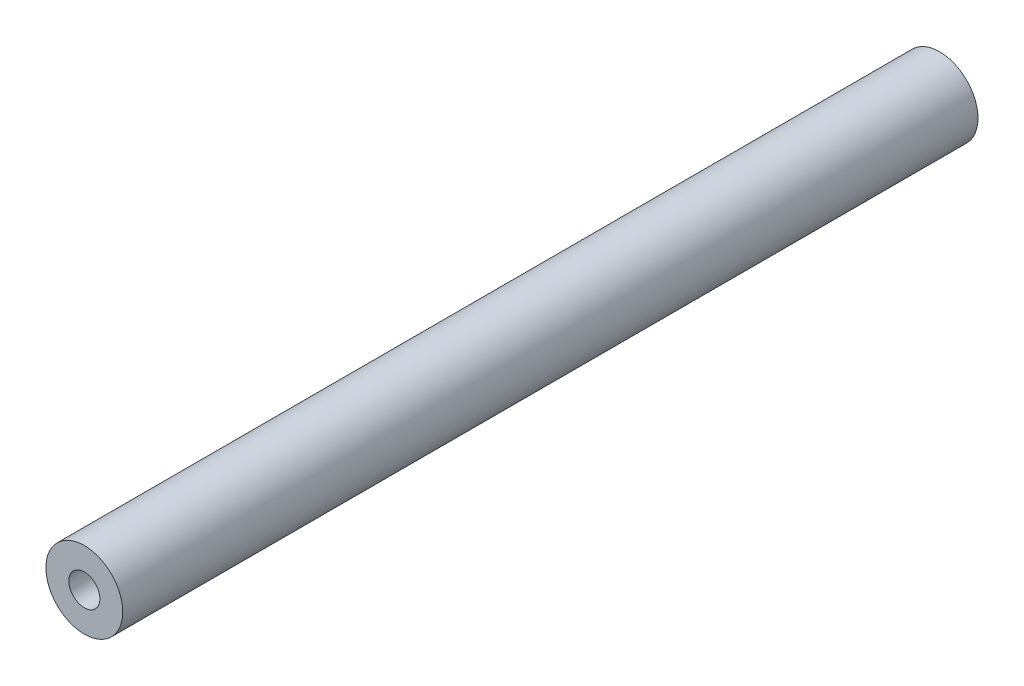
SolidWorks part; units mm, degrees
material "6061-T6 (SS)"
ref_plane "Front Plane" through (0, 0, 0) normal (0, 0, 1) x (1, 0, 0)
ref_plane "Top Plane" through (0, 0, 0) normal (0, 1, 0) x (1, 0, 0)
ref_plane "Right Plane" through (0, 0, 0) normal (1, 0, 0) x (0, 0, -1)
sketch "Sketch1" plane through (0, 0, 0) normal (0, 0, 1) x (1, 0, 0)
  circle A0 centre (0, 0) radius 6.4
  dimension "D1" = 12.8
extrude "Boss-Extrude1" add sketch "Sketch1" along normal blind 142.53
hole_wizard "#6 (0.204) Diameter Hole1" positions "Sketch2" profile "Sketch3" hole size "#6" standard "ANSI Inch"
sketch "Sketch2" plane through (0, 0, 0) normal (0, 0, -1) x (-1, 0, 0)
  point P0 (0, 0)
sketch "Sketch3" plane through (0, 0, 0) normal (1, 0, 0) x (0, 1, 0)
  line L0 (0, 0) -> (0, 31.5567)
  line L1 (0, 31.5567) -> (2.5908, 30)
  line L2 (2.5908, 30) -> (2.5908, 0)
  line L5 (2.5908, 0) -> (0, 0)
  line L10 (0, 31.5567) -> (-2.5908, 30) construction
  line L11 (0, -6.35) -> (0, 107.95) construction
  dimension "Hole Dia." = 5.1816
  dimension "Hole Depth" = 30
  dimension "Drill Angle" = 118
hole_wizard "#6 (0.204) Diameter Hole2" positions "Sketch4" profile "Sketch5" hole size "#6" standard "ANSI Inch"
sketch "Sketch4" plane through (0, 0, 142.53) normal (0, 0, 1) x (1, 0, 0)
  point P0 (0, 0)
sketch "Sketch5" plane through (0, 0, 142.53) normal (1, 0, 0) x (0, -1, 0)
  line L0 (0, 0) -> (0, 31.5567)
  line L1 (0, 31.5567) -> (2.5908, 30)
  line L2 (2.5908, 30) -> (2.5908, 0)
  line L5 (2.5908, 0) -> (0, 0)
  line L10 (0, 31.5567) -> (-2.5908, 30) construction
  line L11 (0, -6.35) -> (0, 107.95) construction
  dimension "Hole Dia." = 5.1816
  dimension "Hole Depth" = 30
  dimension "Drill Angle" = 118
